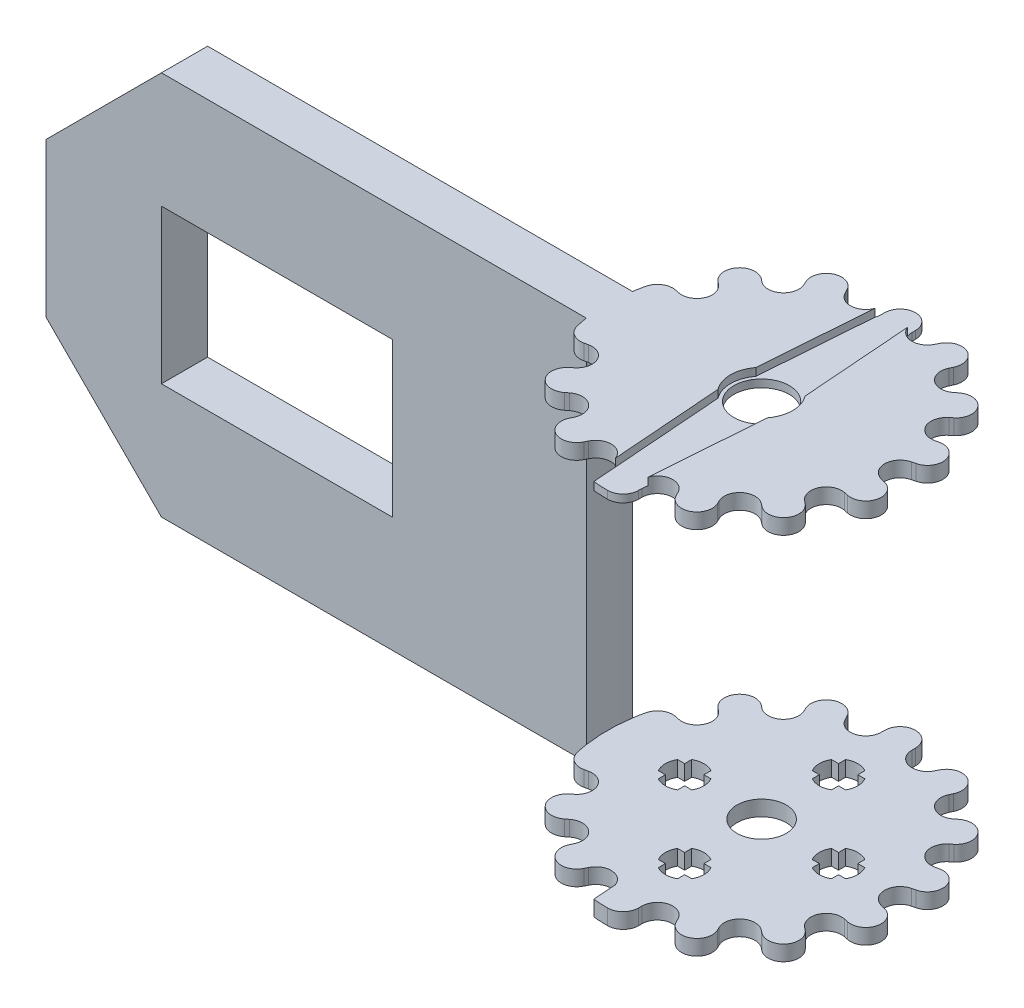
SolidWorks part; units mm, degrees
note: '?' marks a value the reader was unsure of. The reader was unsure of these and kept them because the rebuilt part matched: shared geometry of "Croquis1<3>".
material "PLA"
ref_plane "Alzado" through (0, 0, 0) normal (0, 0, 1) x (1, 0, 0)
ref_plane "Planta" through (0, 0, 0) normal (0, 1, 0) x (1, 0, 0)
ref_plane "Vista lateral" through (0, 0, 0) normal (1, 0, 0) x (0, 0, -1)
sketch "Croquis1" plane through (0, 0, 0) normal (0, 1, 0) x (1, 0, 0)
  line L0 (0, -20) -> (-80, -20)
  line L3 (-80, -20) -> (-90, -20)
  line L6 (-90, -20) -> (-90, -14)
  line L8 (0, 0) -> (-90, 0) construction
  line L9 (-90, 0) -> (-90, 3) construction
  line L10 (-90, -14) -> (-90, 3)
  line L11 (-90, 3) -> (-19.7737, 3)
  circle A0 centre (0, 0) radius 20 construction
  arc A1 (-14.2829, -14) -> (0, -20) centre (0, 0) ccw
  arc A2 (-14.1107, -14.1735) -> (0, -20) centre (0, 0) cw
extrude "Saliente-Extruir1" add sketch "Croquis1" along normal blind 50
extrude "Saliente-Extruir2" add sketch "Croquis1<3>" along normal blind 2 contours A2 A1
sketch "Croquis1<3>" plane through (0, 0, 0) normal (0, 1, 0) x (1, 0, 0) same geometry as "Croquis1"
ref_plane "Plano1" through (0, 25, 0) normal (0, 1, 0) x (1, 0, 0)
mirror "Simetría1" about plane through (0, 25, 0) normal (0, 1, 0) of "Saliente-Extruir2"
sketch "Croquis2" plane through (0, 50, 0) normal (0, 1, 0) x (1, 0, 0)
  line L0 (2, 18) -> (2.0054, 17.5487)
  line L1 (0, 20) -> (0, 16) construction
  line L2 (9.6118, 15.3497) -> (9.4209, 14.9407)
  line L3 (15.3199, 9.6592) -> (14.9705, 9.3736)
  line L4 (17.9937, 2.0555) -> (17.555, 1.9499)
  line L5 (17.1037, -5.9552) -> (16.6625, -5.8601)
  line L6 (12.826, -12.7865) -> (12.4698, -12.5093)
  line L7 (6.008, -17.0852) -> (5.8073, -16.6809)
  line L8 (-2, -18) -> (-2.0054, -17.5487)
  line L9 (-9.6118, -15.3497) -> (-9.4209, -14.9407)
  line L10 (-15.3199, -9.6592) -> (-14.9705, -9.3736)
  line L11 (-17.9937, -2.0555) -> (-17.555, -1.9499)
  line L12 (-17.1037, 5.9552) -> (-16.6625, 5.8601)
  line L13 (-12.826, 12.7865) -> (-12.4698, 12.5093)
  line L14 (-6.008, 17.0852) -> (-5.8073, 16.6809)
  line L15 (-2, 18) -> (-2.0054, 17.5487)
  line L16 (6.008, 17.0852) -> (5.8073, 16.6809)
  line L17 (12.826, 12.7865) -> (12.4698, 12.5093)
  line L18 (17.1037, 5.9552) -> (16.6625, 5.8601)
  line L19 (17.9937, -2.0555) -> (17.555, -1.9499)
  line L20 (15.3199, -9.6592) -> (14.9705, -9.3736)
  line L21 (9.6118, -15.3497) -> (9.4209, -14.9407)
  line L22 (2, -18) -> (2.0054, -17.5487)
  line L23 (-6.008, -17.0852) -> (-5.8073, -16.6809)
  line L24 (-12.826, -12.7865) -> (-12.4698, -12.5093)
  line L25 (-17.1037, -5.9552) -> (-16.6625, -5.8601)
  line L26 (-17.9937, 2.0555) -> (-17.555, 1.9499)
  line L27 (-15.3199, 9.6592) -> (-14.9705, 9.3736)
  line L28 (-9.6118, 15.3497) -> (-9.4209, 14.9407)
  circle A0 centre (0, 0) radius 20 construction
  circle A1 centre (0, 0) radius 16 construction
  circle A2 centre (0, 18) radius 2 construction
  circle A3 centre (4.0054, 17.5487) radius 2 construction
  circle A4 centre (7.8099, 16.2174) radius 2 construction
  circle A5 centre (11.2228, 14.073) radius 2 construction
  circle A6 centre (14.073, 11.2228) radius 2 construction
  circle A7 centre (16.2174, 7.8099) radius 2 construction
  circle A8 centre (17.5487, 4.0054) radius 2 construction
  circle A9 centre (18, 0) radius 2 construction
  circle A10 centre (17.5487, -4.0054) radius 2 construction
  circle A11 centre (16.2174, -7.8099) radius 2 construction
  circle A12 centre (14.073, -11.2228) radius 2 construction
  circle A13 centre (11.2228, -14.073) radius 2 construction
  circle A14 centre (7.8099, -16.2174) radius 2 construction
  circle A15 centre (4.0054, -17.5487) radius 2 construction
  circle A16 centre (0, -18) radius 2 construction
  circle A17 centre (-4.0054, -17.5487) radius 2 construction
  circle A18 centre (-7.8099, -16.2174) radius 2 construction
  circle A19 centre (-11.2228, -14.073) radius 2 construction
  circle A20 centre (-14.073, -11.2228) radius 2 construction
  circle A21 centre (-16.2174, -7.8099) radius 2 construction
  circle A22 centre (-17.5487, -4.0054) radius 2 construction
  circle A23 centre (-18, 0) radius 2 construction
  circle A24 centre (-17.5487, 4.0054) radius 2 construction
  circle A25 centre (-16.2174, 7.8099) radius 2 construction
  circle A26 centre (-14.073, 11.2228) radius 2 construction
  circle A27 centre (-11.2228, 14.073) radius 2 construction
  circle A28 centre (-7.8099, 16.2174) radius 2 construction
  circle A29 centre (-4.0054, 17.5487) radius 2 construction
  arc A30 (-2, 18) -> (2, 18) centre (0, 18) cw
  arc A31 (2.0054, 17.5487) -> (4.0054, 15.5487) centre (4.0054, 17.5487) ccw
  arc A32 (6.008, 17.0852) -> (9.6118, 15.3497) centre (7.8099, 16.2174) cw
  arc A33 (9.4209, 14.9407) -> (10.355, 12.271) centre (11.2228, 14.073) ccw
  arc A34 (12.826, 12.7865) -> (15.3199, 9.6592) centre (14.073, 11.2228) cw
  arc A35 (14.9705, 9.3736) -> (14.6538, 6.5629) centre (16.2174, 7.8099) ccw
  arc A36 (17.1037, 5.9552) -> (17.9937, 2.0555) centre (17.5487, 4.0054) cw
  arc A37 (17.555, 1.9499) -> (16.0501, -0.445) centre (18, 0) ccw
  arc A38 (17.9937, -2.0555) -> (17.1037, -5.9552) centre (17.5487, -4.0054) cw
  arc A39 (16.6625, -5.8601) -> (14.2676, -7.3649) centre (16.2174, -7.8099) ccw
  arc A40 (15.3199, -9.6592) -> (12.826, -12.7865) centre (14.073, -11.2228) cw
  arc A41 (12.4698, -12.5093) -> (9.6592, -12.826) centre (11.2228, -14.073) ccw
  arc A42 (9.6118, -15.3497) -> (6.008, -17.0852) centre (7.8099, -16.2174) cw
  arc A43 (5.8073, -16.6809) -> (3.1376, -15.7468) centre (4.0054, -17.5487) ccw
  arc A44 (2, -18) -> (-2, -18) centre (0, -18) cw
  arc A45 (-2.0054, -17.5487) -> (-4.0054, -15.5487) centre (-4.0054, -17.5487) ccw
  arc A46 (-6.008, -17.0852) -> (-9.6118, -15.3497) centre (-7.8099, -16.2174) cw
  arc A47 (-9.4209, -14.9407) -> (-10.355, -12.271) centre (-11.2228, -14.073) ccw
  arc A48 (-12.826, -12.7865) -> (-15.3199, -9.6592) centre (-14.073, -11.2228) cw
  arc A49 (-14.9705, -9.3736) -> (-14.6538, -6.5629) centre (-16.2174, -7.8099) ccw
  arc A50 (-17.1037, -5.9552) -> (-17.9937, -2.0555) centre (-17.5487, -4.0054) cw
  arc A51 (-17.555, -1.9499) -> (-16.0501, 0.445) centre (-18, 0) ccw
  arc A52 (-17.9937, 2.0555) -> (-17.1037, 5.9552) centre (-17.5487, 4.0054) cw
  arc A53 (-16.6625, 5.8601) -> (-14.2676, 7.3649) centre (-16.2174, 7.8099) ccw
  arc A54 (-15.3199, 9.6592) -> (-12.826, 12.7865) centre (-14.073, 11.2228) cw
  arc A55 (-12.4698, 12.5093) -> (-9.6592, 12.826) centre (-11.2228, 14.073) ccw
  arc A56 (-9.6118, 15.3497) -> (-6.008, 17.0852) centre (-7.8099, 16.2174) cw
  arc A57 (-5.8073, 16.6809) -> (-3.1376, 15.7468) centre (-4.0054, 17.5487) ccw
  arc A58 (-2.0054, 17.5487) -> (-3.1376, 15.7468) centre (-4.0054, 17.5487) cw
  arc A59 (5.8073, 16.6809) -> (4.0054, 15.5487) centre (4.0054, 17.5487) cw
  arc A60 (12.4698, 12.5093) -> (10.355, 12.271) centre (11.2228, 14.073) cw
  arc A61 (16.6625, 5.8601) -> (14.6538, 6.5629) centre (16.2174, 7.8099) cw
  arc A62 (17.555, -1.9499) -> (16.0501, -0.445) centre (18, 0) cw
  arc A63 (14.9705, -9.3736) -> (14.2676, -7.3649) centre (16.2174, -7.8099) cw
  arc A64 (9.4209, -14.9407) -> (9.6592, -12.826) centre (11.2228, -14.073) cw
  arc A65 (2.0054, -17.5487) -> (3.1376, -15.7468) centre (4.0054, -17.5487) cw
  arc A66 (-5.8073, -16.6809) -> (-4.0054, -15.5487) centre (-4.0054, -17.5487) cw
  arc A67 (-12.4698, -12.5093) -> (-10.355, -12.271) centre (-11.2228, -14.073) cw
  arc A68 (-16.6625, -5.8601) -> (-14.6538, -6.5629) centre (-16.2174, -7.8099) cw
  arc A69 (-17.555, 1.9499) -> (-16.0501, 0.445) centre (-18, 0) cw
  arc A70 (-14.9705, 9.3736) -> (-14.2676, 7.3649) centre (-16.2174, 7.8099) cw
  arc A71 (-9.4209, 14.9407) -> (-9.6592, 12.826) centre (-11.2228, 14.073) cw
  point P65 (0, 0)
  point P150 (0, 0)
  point P206 (0, 0)
  dimension "D1" = 28
  dimension "D2" = 14
  dimension "D3" = 14
extrude "Cortar-Extruir2" cut sketch "Croquis2" against normal blind 2 contours A70 L27 A54 A2 A52 L12 A53 | A71 L28 A56 A2 A54 L13 A55 | A58 L15 A30 A2 A56 L14 A57 | A59 L16 A32 A2 A30 L0 A31 | A60 L17 A34 A2 A32 L2 A33 | A61 L18 A36 A2 A34 L3 A35 | A62 L19 A38 A2 A36 L4 A37 | A63 L20 A40 A2 A38 L5 A39 | A64 L21 A42 A2 A40 L6 A41 | A65 L22 A44 A2 A42 L7 A43
mirror "Simetría2" about plane through (0, 25, 0) normal (0, 1, 0) of "Cortar-Extruir2"
sketch "Croquis3" plane through (0, 50, 0) normal (0, 1, 0) x (1, 0, 0)
  line L0 (0, 0) -> (0, -20.1816) construction
  line L1 (0, 0) -> (3.6, 0) construction
  line L2 (0, 0) -> (0, -2.4507) construction
  line L3 (0, -2.4507) -> (3.2094, -2.4507) construction
  line L4 (-1.8774, -20.1816) -> (1.8774, -20.1816)
  line L5 (3.2094, -2.4507) -> (1.8774, -20.1816)
  line L6 (-1.8774, 20.1816) -> (1.8774, 20.1816)
  line L7 (3.2094, 2.4507) -> (1.8774, 20.1816)
  line L8 (-3.2094, -2.4507) -> (-1.8774, -20.1816)
  line L9 (-3.2094, 2.4507) -> (-1.8774, 20.1816)
  circle A0 centre (0, 0) radius 4.0381 construction
  arc A1 (3.2094, 2.4507) -> (3.2094, -2.4507) centre (0, 0) cw
  arc A2 (-3.2094, 2.4507) -> (-3.2094, -2.4507) centre (0, 0) ccw
  point P16 (0, 20.1816)
extrude "Cortar-Extruir3" cut sketch "Croquis3" against normal blind 1
sketch "Croquis4" plane through (0, 49, 0) normal (0, 1, 0) x (1, 0, 0)
  circle A0 centre (0, 0) radius 3.6
  point P4 (0, 0)
extrude "Cortar-Extruir4" cut sketch "Croquis4" against normal blind 11
sketch "Croquis5" plane through (0, 0, 20) normal (0, 0, 1) x (1, 0, 0)
  line L1 (0, 48) -> (0, 2) construction
  line L5 (22, 25) -> (-22, 25) construction
  line L8 (0, 6) -> (0, 3.9935) construction
  line L9 (0, 3.9935) -> (-28.15, 3.9935)
  line L10 (-28.15, 25) -> (0, 25) construction
  line L11 (-28.15, 46.0065) -> (-28.15, 3.9935)
  line L12 (0, 46.0065) -> (-28.15, 46.0065)
  line L13 (0, 46.0065) -> (0, 25)
  line L14 (0, 25) -> (0, 3.9935)
  point P12 (-28.15, 25)
extrude "Cortar-Extruir5" cut sketch "Croquis5" against normal blind 10
sketch "Croquis6" plane through (0, 0, 0) normal (0, -1, 0) x (1, 0, 0)
  circle A0 centre (0, 0) radius 3.2
extrude "Cortar-Extruir6" cut sketch "Croquis6" against normal up to next
sketch "Croquis7" plane through (0, 0, 20) normal (0, 0, 1) x (1, 0, 0)
  line L0 (-75, 0) -> (-90, 0)
  line L1 (-80, 25) -> (-90, 25) construction
  line L3 (-90, 15) -> (-90, 0)
  line L8 (-90, 50) -> (-90, 0) construction
  line L13 (-90, 25) -> (-90, 35)
  line L14 (-90, 35) -> (-90, 50) construction
  line L16 (-90, 35) -> (-75, 35) construction
  line L18 (-90, 35) -> (-75, 50)
  line L19 (-75, 35) -> (-90, 35) construction
  line L20 (-75, 35) -> (-75, 50) construction
  line L21 (-75, 50) -> (-90, 50)
  line L22 (-90, 35) -> (-90, 50)
  line L23 (-80, 25) -> (-75, 25) construction
  line L24 (-75, 25) -> (-75, 15) construction
  line L25 (-90, 15) -> (-75, 0)
  line L26 (-75, 35) -> (-45, 35)
  line L27 (-75, 35) -> (-75, 15)
  line L28 (-75, 15) -> (-45, 15)
  line L29 (-45, 35) -> (-45, 15)
  line M8 (-1.8911, 50) -> (-90, 50)
  line M10 (-90, 0) -> (0, 0)
  line M13 (-90, 50) -> (-90, 0)
extrude "Cortar-Extruir7" cut sketch "Croquis7" against normal up to next contours L29 L26 L27 L28 | L18 M13 M8 | L25 M13 M10
ref_plane "Plano2" through (0, 25, 0) normal (0, 1, 0) x (1, 0, 0)
sketch "Croquis8" plane through (0, 25, 0) normal (0, 1, 0) x (1, 0, 0)
  line L1 (-94.0142, 23.0405) -> (21.6376, 23.0405)
  line L2 (-94.0142, 23.0405) -> (-94.0142, -23.1689)
  line L3 (-94.0142, -23.1689) -> (21.6376, -23.1689)
  line L4 (21.6376, 23.0405) -> (21.6376, -23.1689)
ref_axis "Eje1" through (0, 0, 0) along (0, 1, 0)?
sketch "Croquis9" plane through (0, 50, 0) normal (0, 1, 0) x (1, 0, 0)
  line L0 (-20, 0) -> (-90, 0) construction
  line L1 (-90, 0) -> (-90, -3) construction
  line L2 (-90, -14) -> (-90, 3) construction
  line L3 (-90, -3) -> (-19.7737, -3)
  line L4 (-90, -3) -> (-90, -20)
  line L5 (-90, -20) -> (0, -20)
  circle A0 centre (0, 0) radius 20 construction
  arc A1 (-19.7737, -3) -> (0, -20) centre (0, 0) ccw
extrude "Cortar-Extruir8" cut sketch "Croquis9" against normal up to next
sketch "Croquis10" plane through (0, 50, 0) normal (0, 1, 0) x (1, 0, 0)
  line L0 (-17.1037, -5.9552) -> (-16.6625, -5.8601)
  line L1 (-14.9705, -9.3736) -> (-15.3199, -9.6592)
  line L2 (-12.826, -12.7865) -> (-12.4698, -12.5093)
  line L3 (-9.4209, -14.9407) -> (-9.6118, -15.3497)
  line L4 (-6.008, -17.0852) -> (-5.8073, -16.6809)
  line L5 (-2.0054, -17.5487) -> (-2, -18)
  arc A0 (-5.8073, -16.6809) -> (-2.0054, -17.5487) centre (-4.0054, -17.5487) cw
  arc A1 (0, -20) -> (-2, -18) centre (0, -18) cw
  arc A2 (-6.008, -17.0852) -> (-9.6118, -15.3497) centre (-7.8099, -16.2174) cw
  arc A3 (-12.4698, -12.5093) -> (-9.4209, -14.9407) centre (-11.2228, -14.073) cw
  arc A4 (-12.826, -12.7865) -> (-15.3199, -9.6592) centre (-14.073, -11.2228) cw
  arc A5 (-14.9705, -9.3736) -> (-16.6625, -5.8601) centre (-16.2174, -7.8099) ccw
  arc A6 (-17.1037, -5.9552) -> (-19.4986, -4.4504) centre (-17.5487, -4.0054) cw
  arc A7 (-17.9937, -2.0555) -> (-17.1037, -5.9552) centre (-17.5487, -4.0054) ccw construction
  circle A8 centre (0, 0) radius 20
  arc M2 (-19.7737, -3) -> (-1.8979, -19.9097) centre (0, 0) ccw
  line M3 (-1.8979, -19.9097) -> (-3.2094, -2.4507)
extrude "Cortar-Extruir9" cut sketch "Croquis10" against normal through all contours L4 A2 A0 M2 M3 | L2 A4 A2 L3 A3 M2 | L0 A6 A4 L1 A5 M2
sketch "Croquis11" plane through (0, 0, 0) normal (0, -1, 0) x (1, 0, 0)
  line L0 (0, 10) -> (0, 12.5) construction
  line L1 (0, 10) -> (2.5, 10) construction
  line L2 (2.5, 10) -> (1.25, 10) construction
  line L3 (1.25, 10) -> (1.25, 12.1651) construction
  line L4 (0, 11.2782) -> (0, 11.25) construction
  line L5 (0, 11.25) -> (2.1651, 11.25) construction
  line L6 (1.25, 12.1651) -> (1.25, 11.25)
  line L7 (1.25, 11.25) -> (2.1651, 11.25)
  line L8 (2.1651, 8.75) -> (1.25, 8.75)
  line L9 (1.25, 8.75) -> (1.25, 7.8349)
  line L10 (-1.25, 7.8349) -> (-1.25, 8.75)
  line L11 (-1.25, 8.75) -> (-2.1651, 8.75)
  line L12 (-2.1651, 11.25) -> (-1.25, 11.25)
  line L13 (-1.25, 11.25) -> (-1.25, 12.1651)
  line L14 (11.25, 1.25) -> (12.1651, 1.25)
  line L15 (11.25, 2.1651) -> (11.25, 1.25)
  line L16 (8.75, 1.25) -> (8.75, 2.1651)
  line L17 (7.8349, 1.25) -> (8.75, 1.25)
  line L18 (8.75, -1.25) -> (7.8349, -1.25)
  line L19 (8.75, -2.1651) -> (8.75, -1.25)
  line L20 (11.25, -1.25) -> (11.25, -2.1651)
  line L21 (12.1651, -1.25) -> (11.25, -1.25)
  line L22 (1.25, -11.25) -> (1.25, -12.1651)
  line L23 (2.1651, -11.25) -> (1.25, -11.25)
  line L24 (1.25, -8.75) -> (2.1651, -8.75)
  line L25 (1.25, -7.8349) -> (1.25, -8.75)
  line L26 (-1.25, -8.75) -> (-1.25, -7.8349)
  line L27 (-2.1651, -8.75) -> (-1.25, -8.75)
  line L28 (-1.25, -11.25) -> (-2.1651, -11.25)
  line L29 (-1.25, -12.1651) -> (-1.25, -11.25)
  line L30 (-11.25, -1.25) -> (-12.1651, -1.25)
  line L31 (-11.25, -2.1651) -> (-11.25, -1.25)
  line L32 (-8.75, -1.25) -> (-8.75, -2.1651)
  line L33 (-7.8349, -1.25) -> (-8.75, -1.25)
  line L34 (-8.75, 1.25) -> (-7.8349, 1.25)
  line L35 (-8.75, 2.1651) -> (-8.75, 1.25)
  line L36 (-11.25, 1.25) -> (-11.25, 2.1651)
  line L37 (-12.1651, 1.25) -> (-11.25, 1.25)
  circle A0 centre (0, 0) radius 10 construction
  circle A1 centre (0, 10) radius 2.5 construction
  arc A2 (0, 12.5) -> (1.25, 12.1651) centre (0, 10) cw
  arc A3 (2.1651, 11.25) -> (2.5, 10) centre (0, 10) cw
  arc A4 (2.5, 10) -> (2.1651, 8.75) centre (0, 10) cw
  arc A5 (1.25, 7.8349) -> (0, 7.5) centre (0, 10) cw
  arc A6 (0, 7.5) -> (-1.25, 7.8349) centre (0, 10) cw
  arc A7 (-2.1651, 8.75) -> (-2.5, 10) centre (0, 10) cw
  arc A8 (-2.5, 10) -> (-2.1651, 11.25) centre (0, 10) cw
  arc A9 (-1.25, 12.1651) -> (0, 12.5) centre (0, 10) cw
  arc A10 (12.1651, 1.25) -> (12.5, 0) centre (10, 0) cw
  arc A11 (12.5, 0) -> (12.1651, -1.25) centre (10, 0) cw
  arc A12 (10, 2.5) -> (11.25, 2.1651) centre (10, 0) cw
  arc A13 (8.75, 2.1651) -> (10, 2.5) centre (10, 0) cw
  arc A14 (7.5, 0) -> (7.8349, 1.25) centre (10, 0) cw
  arc A15 (7.8349, -1.25) -> (7.5, 0) centre (10, 0) cw
  arc A16 (10, -2.5) -> (8.75, -2.1651) centre (10, 0) cw
  arc A17 (11.25, -2.1651) -> (10, -2.5) centre (10, 0) cw
  arc A18 (1.25, -12.1651) -> (0, -12.5) centre (0, -10) cw
  arc A19 (0, -12.5) -> (-1.25, -12.1651) centre (0, -10) cw
  arc A20 (2.5, -10) -> (2.1651, -11.25) centre (0, -10) cw
  arc A21 (2.1651, -8.75) -> (2.5, -10) centre (0, -10) cw
  arc A22 (0, -7.5) -> (1.25, -7.8349) centre (0, -10) cw
  arc A23 (-1.25, -7.8349) -> (0, -7.5) centre (0, -10) cw
  arc A24 (-2.5, -10) -> (-2.1651, -8.75) centre (0, -10) cw
  arc A25 (-2.1651, -11.25) -> (-2.5, -10) centre (0, -10) cw
  arc A26 (-12.1651, -1.25) -> (-12.5, 0) centre (-10, 0) cw
  arc A27 (-12.5, 0) -> (-12.1651, 1.25) centre (-10, 0) cw
  arc A28 (-10, -2.5) -> (-11.25, -2.1651) centre (-10, 0) cw
  arc A29 (-8.75, -2.1651) -> (-10, -2.5) centre (-10, 0) cw
  arc A30 (-7.5, 0) -> (-7.8349, -1.25) centre (-10, 0) cw
  arc A31 (-7.8349, 1.25) -> (-7.5, 0) centre (-10, 0) cw
  arc A32 (-10, 2.5) -> (-8.75, 2.1651) centre (-10, 0) cw
  arc A33 (-11.25, 2.1651) -> (-10, 2.5) centre (-10, 0) cw
  point P33 (0, 10)
  point P92 (0, 0)
  dimension "D1" = 4
  dimension "D2" = 4
extrude "Cortar-Extruir10" cut sketch "Croquis11" against normal up to next contours A9 L13 L12 A8 A7 L11 L10 A6 A5 L9 L8 A4 A3 L7 L6 A2 | A33 L36 L37 A27 A26 L30 L31 A28 A29 L32 L33 A30 A31 L34 L35 A32 | A17 L20 L21 A11 A10 L14 L15 A12 A13 L16 L17 A14 A15 L18 L19 A16 | A25 L28 L29 A19 A18 L22 L23 A20 A21 L24 L25 A22 A23 L26 L27 A24
sketch "Croquis12" plane through (0, 25, 0) normal (0, 1, 0) x (1, 0, 0)
  line L1 (-102.1853, 35.109) -> (25.548, 35.109)
  line L2 (-102.1853, 35.109) -> (-102.1853, -26.1701)
  line L3 (-102.1853, -26.1701) -> (25.548, -26.1701)
  line L4 (25.548, 35.109) -> (25.548, -26.1701)
